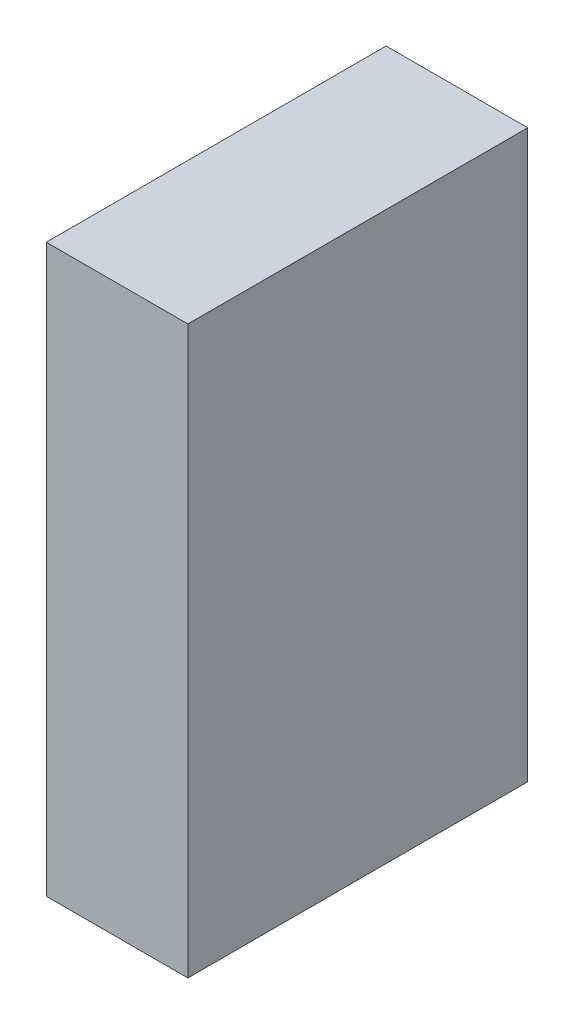
SolidWorks part; units mm, degrees
ref_plane "Front Plane" through (0, 0, 0) normal (0, 0, 1) x (1, 0, 0)
ref_plane "Top Plane" through (0, 0, 0) normal (0, 1, 0) x (1, 0, 0)
ref_plane "Right Plane" through (0, 0, 0) normal (1, 0, 0) x (0, 0, -1)
sketch "Sketch1" plane through (0, 0, 0) normal (0, 0, 1) x (1, 0, 0)
  line L1 (0, 0) -> (15.875, 0)
  line L2 (0, 0) -> (0, 63.5)
  line L3 (0, 63.5) -> (15.875, 63.5)
  line L4 (15.875, 0) -> (15.875, 63.5)
  dimension "D1" = 63.5
  dimension "D2" = 15.875
extrude "Boss-Extrude1" add sketch "Sketch1" along normal blind 38.1
sketch "Sketch2" plane through (0, 0, 0) normal (-1, 0, 0) x (0, 0, 1)
  line L0 (-42.0248, 5.2309) -> (-42.0248, 36.9809)
  line L1 (-49.0733, 42.4721) -> (-49.0733, 29.6589)
  line L2 (-34.9763, 29.6589) -> (-34.9763, 42.4721)
  line L3 (-49.0733, 36.0655) -> (-34.9763, 36.0655)
  line L4 (-49.0733, 29.6589) -> (-49.0733, 5.2309)
  line L5 (-34.9763, 29.6589) -> (-34.9763, 5.2309)
  arc A0 (-49.0733, 42.4721) -> (-34.9763, 42.4721) centre (-42.0248, 36.9809) cw
  arc A1 (-49.0733, 29.6589) -> (-34.9763, 29.6589) centre (-42.0248, 35.1501) ccw
  point P10 (-42.0248, 45.9159)
  dimension "D6" = 29.9192
  dimension "D1" = 31.75
  dimension "D2" = 12.8132
  dimension "D3" = 12.8132
  dimension "D4" = 14.097
  dimension "D5" = 8.935
